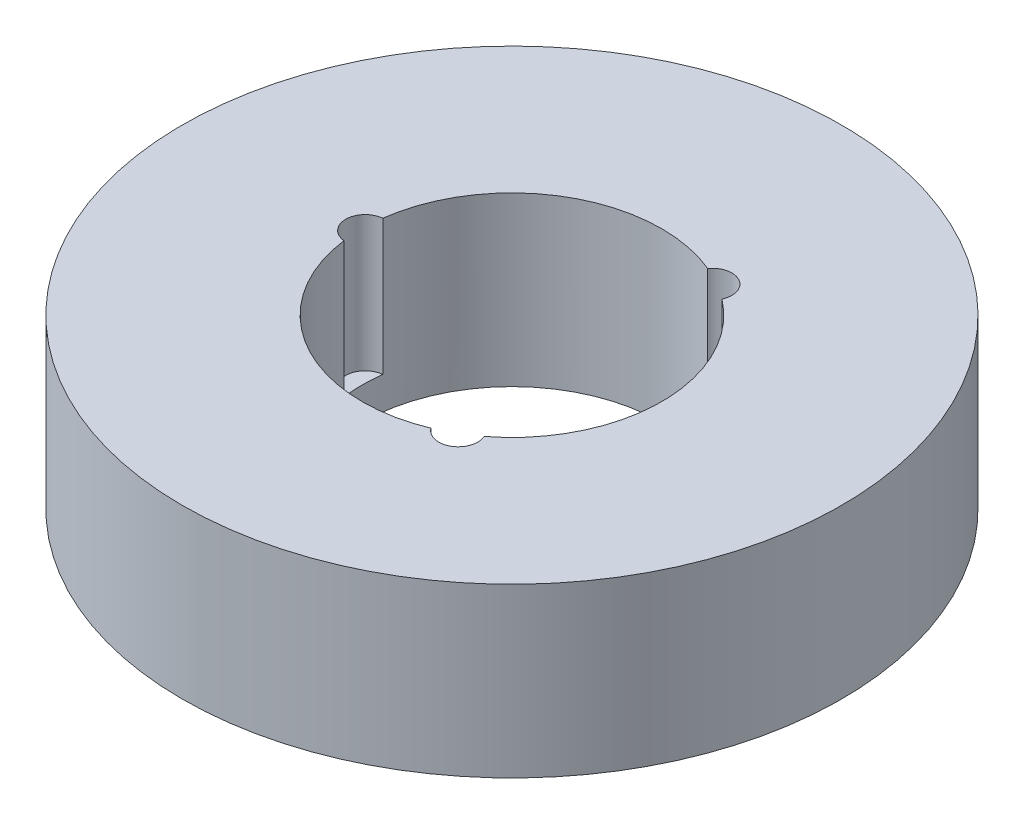
SolidWorks part; units mm, degrees
ref_plane "Front Plane" through (0, 0, 0) normal (0, 0, 1) x (1, 0, 0)
ref_plane "Top Plane" through (0, 0, 0) normal (0, 1, 0) x (1, 0, 0)
ref_plane "Right Plane" through (0, 0, 0) normal (1, 0, 0) x (0, 0, -1)
sketch "Sketch1" plane through (0, 0, 0) normal (0, 1, 0) x (1, 0, 0)
  circle A0 centre (0, 0) radius 55
  dimension "FLANGE_OD" = 110
extrude "Boss-Extrude1" add sketch "Sketch1" along normal blind 28
sketch "Sketch2" plane through (0, 0, 0) normal (0, 1, 0) x (1, 0, 0)
  circle A0 centre (0, 0) radius 25
  dimension "BORE_D" = 50
extrude "Cut-Extrude1" cut sketch "Sketch2" along normal through all
sketch "Sketch3" plane through (0, 28, 0) normal (0, 1, 0) x (1, 0, 0)
  circle A0 centre (0, 0) radius 24.4827 construction
  circle A1 centre (-24.4827, 0) radius 3.2557
  dimension "BOLT_D" = 6.5114
  dimension "BOLT_PCD" = 48.9654
extrude "Cut-Extrude2" cut sketch "Sketch3" against normal blind 22.5809
pattern_circular "CirPattern1" count 3 over 360 about axis through (0, 0, 0) along (0, 1, 0) of "Cut-Extrude2"
